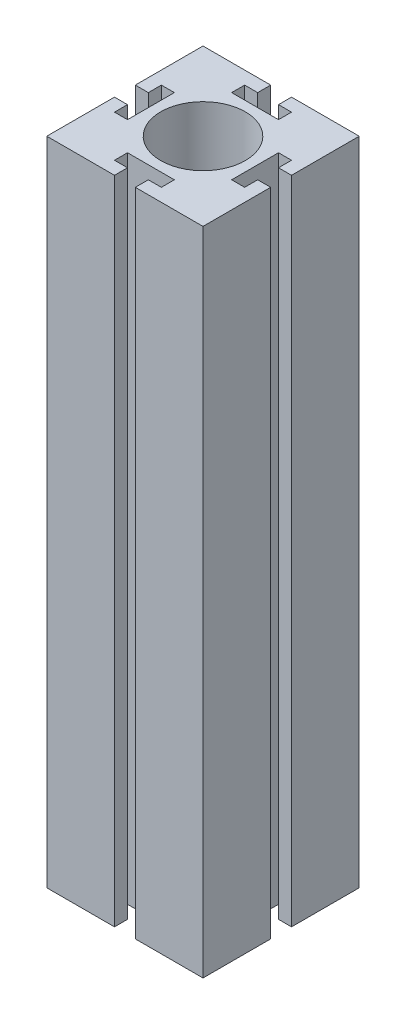
SolidWorks part; units mm, degrees
ref_plane "Plan de face" through (0, 0, 0) normal (0, 0, 1) x (1, 0, 0)
ref_plane "Plan de dessus" through (0, 0, 0) normal (0, 1, 0) x (1, 0, 0)
ref_plane "Plan de droite" through (0, 0, 0) normal (1, 0, 0) x (0, 0, -1)
sketch "Esquisse1" plane through (0, 0, 0) normal (0, 1, 0) x (1, 0, 0)
  line L1 (-6, 6) -> (6, 6)
  line L2 (-6, 6) -> (-6, -6)
  line L3 (-6, -6) -> (6, -6)
  line L4 (6, 6) -> (6, -6)
  dimension "D1" = 12
  dimension "D2" = 12
  dimension "D3" = 6
  dimension "D4" = 6
extrude "Boss.-Extru.1" add sketch "Esquisse1" along normal blind 50
sketch "Esquisse2" plane through (0, 50, 0) normal (0, 1, 0) x (1, 0, 0)
  line L0 (-5, -0.8) -> (-5, -1.8)
  line L1 (-6, 0.8) -> (-5, 0.8)
  line L2 (-6, 0.8) -> (-6, -0.8)
  line L3 (-6, -0.8) -> (-5, -0.8)
  line L5 (-5, 1.8) -> (-4, 1.8)
  line L6 (-5, 1.8) -> (-5, 0.8)
  line L7 (-5, -1.8) -> (-4, -1.8)
  line L8 (-4, 1.8) -> (-4, -1.8)
  line L9 (-6, 6) -> (-6, -6) construction
  line L10 (1.8, 5) -> (1.8, 4)
  line L11 (1.8, 4) -> (-1.8, 4)
  line L12 (-1.8, 5) -> (-1.8, 4)
  line L13 (-0.8, 5) -> (-1.8, 5)
  line L14 (-0.8, 6) -> (-0.8, 5)
  line L15 (0.8, 6) -> (-0.8, 6)
  line L16 (0.8, 6) -> (0.8, 5)
  line L17 (1.8, 5) -> (0.8, 5)
  line L18 (5, -1.8) -> (4, -1.8)
  line L19 (4, -1.8) -> (4, 1.8)
  line L20 (5, 1.8) -> (4, 1.8)
  line L21 (5, 0.8) -> (5, 1.8)
  line L22 (6, 0.8) -> (5, 0.8)
  line L23 (6, -0.8) -> (6, 0.8)
  line L24 (6, -0.8) -> (5, -0.8)
  line L25 (5, -1.8) -> (5, -0.8)
  line L26 (-1.8, -5) -> (-1.8, -4)
  line L27 (-1.8, -4) -> (1.8, -4)
  line L28 (1.8, -5) -> (1.8, -4)
  line L29 (0.8, -5) -> (1.8, -5)
  line L30 (0.8, -6) -> (0.8, -5)
  line L31 (-0.8, -6) -> (0.8, -6)
  line L32 (-0.8, -6) -> (-0.8, -5)
  line L33 (-1.8, -5) -> (-0.8, -5)
  point P38 (0, 0)
  dimension "D1" = 1.6
  dimension "D2" = 1
  dimension "D3" = 1
  dimension "D4" = 0
  dimension "D5" = 0.8
  dimension "D6" = 1
  dimension "D7" = 2
  dimension "D8" = 4
extrude "Enlèv. mat.-Extru.1" cut sketch "Esquisse2" against normal up to vertex (50 mm away) up to point (0, 0, 0)
sketch "Esquisse3" plane through (0, 50, 0) normal (0, 1, 0) x (1, 0, 0)
  circle A0 centre (0, 0) radius 3.25
  dimension "D1" = 6.5
extrude "Enlèv. mat.-Extru.2" cut sketch "Esquisse3" against normal blind 47
sketch "Esquisse4" plane through (0, 3, 0) normal (0, 1, 0) x (1, 0, 0)
  circle A0 centre (0, 0) radius 1
  dimension "D1" = 2
extrude "Enlèv. mat.-Extru.3" cut sketch "Esquisse4" against normal up to surface (3 mm away) up to face at (0, 0, 0)
